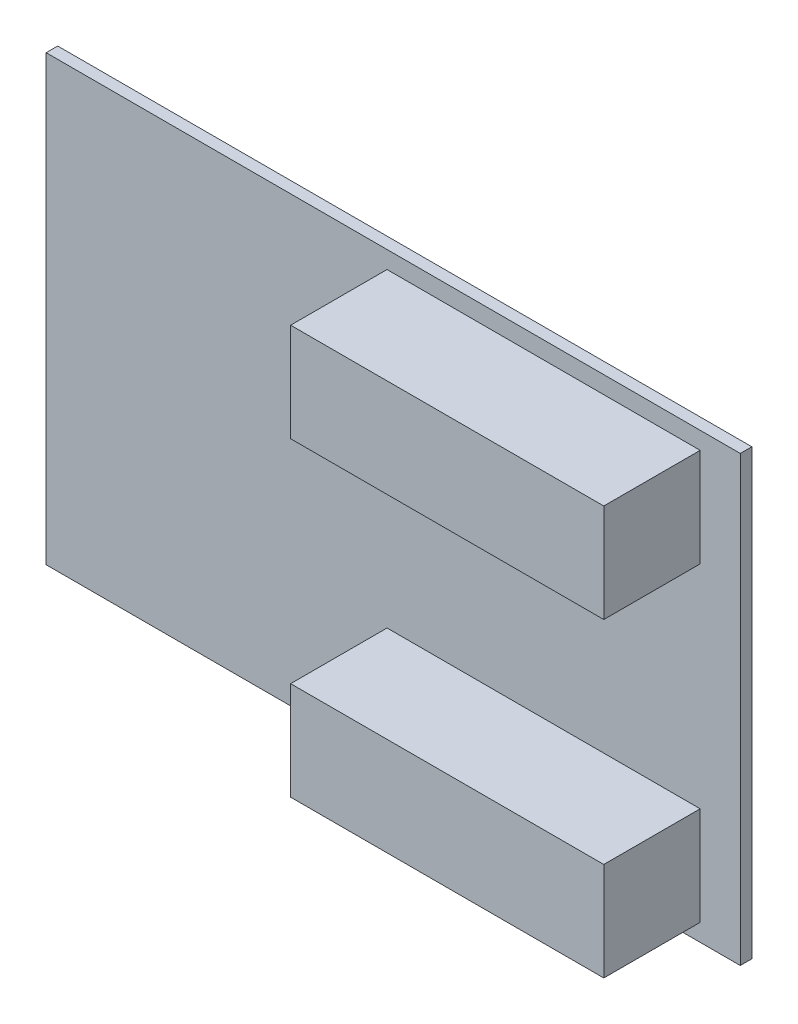
SolidWorks part; units mm, degrees
ref_plane "前视基准面" through (0, 0, 0) normal (0, 0, 1) x (1, 0, 0)
ref_plane "上视基准面" through (0, 0, 0) normal (0, 1, 0) x (1, 0, 0)
ref_plane "右视基准面" through (0, 0, 0) normal (1, 0, 0) x (0, 0, -1)
sketch "草图1" plane through (0, 0, 0) normal (0, 0, 1) x (1, 0, 0)
  line L1 (-90, 57.5) -> (90, 57.5)
  line L2 (-90, 57.5) -> (-90, -57.5)
  line L3 (-90, -57.5) -> (90, -57.5)
  line L4 (90, 57.5) -> (90, -57.5)
  line L5 (-90, 57.5) -> (90, -57.5) construction
  line L6 (-90, -57.5) -> (90, 57.5) construction
  point P0 (0, 0)
  dimension "D1" = 115
  dimension "D2" = 180
extrude "凸台-拉伸1" add sketch "草图1" along normal blind 3
sketch "草图7" plane through (0, 0, 0) normal (0, 0, -1) x (-1, 0, 0)
  line L0 (-90, 57.5) -> (90, 57.5) construction
  line L1 (-77.1, 50.5) -> (-0.9, 50.5)
  line L2 (-77.1, 50.5) -> (-77.1, 30)
  line L3 (-77.1, 30) -> (-0.9, 30)
  line L4 (-0.9, 50.5) -> (-0.9, 30)
  line L6 (-90, -57.5) -> (-90, 57.5) construction
  dimension "D1" = 20.5
  dimension "D2" = 76.2
  dimension "D3" = 7
  dimension "D4" = 12.9
extrude "电池位切除-拉伸3" cut sketch "草图7" against normal up to next
sketch "草图8" plane through (0, 0, 3) normal (0, 0, 1) x (1, 0, 0)
  line L12 (77.1, 50.5) -> (77.1, 30) construction
  line L13 (-1.6, 53) -> (79.6, 53)
  line L14 (-1.6, 53) -> (-1.6, 27.5)
  line L15 (-1.6, 27.5) -> (79.6, 27.5)
  line L16 (79.6, 53) -> (79.6, 27.5)
  line L17 (0.9, 30) -> (0.9, 50.5) construction
  line L18 (0.9, 50.5) -> (77.1, 50.5) construction
  line L19 (77.1, 30) -> (0.9, 30) construction
  line L20 (0.9, 50.5) -> (77.1, 50.5)
  line L21 (77.1, 30) -> (0.9, 30)
  line L22 (77.1, 50.5) -> (77.1, 30)
  line L23 (0.9, 30) -> (0.9, 50.5) construction
  line L24 (0.9, 30) -> (0.9, 50.5)
  dimension "D1" = 2.5
  dimension "D2" = 2.5
  dimension "D3" = 2.5
  dimension "D4" = 2.5
extrude "凸台-拉伸2" add sketch "草图8" along normal blind 25
sketch "草图9" plane through (0, 0, 28) normal (0, 0, 1) x (1, 0, 0)
  line L0 (79.6, 53) -> (-1.6, 53) construction
  line L5 (79.6, 53) -> (-1.6, 53)
  line L6 (-1.6, 27.5) -> (79.6, 27.5) construction
  line L7 (-1.6, 27.5) -> (79.6, 27.5)
  line L8 (79.6, 27.5) -> (79.6, 53) construction
  line L9 (79.6, 27.5) -> (79.6, 53)
  line L10 (-1.6, 53) -> (-1.6, 27.5) construction
  line L11 (-1.6, 53) -> (-1.6, 27.5)
extrude "凸台-拉伸3" add sketch "草图9" against normal blind 2.5
sketch "草图4" plane through (0, 0, 0) normal (0, 0, -1) x (-1, 0, 0)
  line L0 (-0.9, 30) -> (-0.9, 50.5) construction
  line L5 (-0.9, 40.25) -> (84.6307, 40.25) construction
  line L10 (83.2374, -53.4277) -> (79.3374, -53.4277) construction
  line L11 (83.2374, -49.6277) -> (83.2374, -53.4277) construction
  line L12 (79.3374, -49.6277) -> (83.2374, -49.6277) construction
  line L29 (-0.9, 36.25) -> (3.1, 36.25)
  line L30 (3.1, 36.25) -> (3.1, 44.25)
  line L31 (3.1, 44.25) -> (-0.9, 44.25)
  line L32 (-0.9, 44.25) -> (-0.9, 36.25)
  dimension "D1" = 8
  dimension "D2" = 4
extrude "切除-拉伸2" cut sketch "草图4" along normal blind 1.6 from surface starting at face at (0, 0, 3)
mirror "镜向1" about plane through (0, 0, 0) normal (0, 1, 0) of "切除-拉伸2", "凸台-拉伸3", "凸台-拉伸2", "电池位切除-拉伸3"
